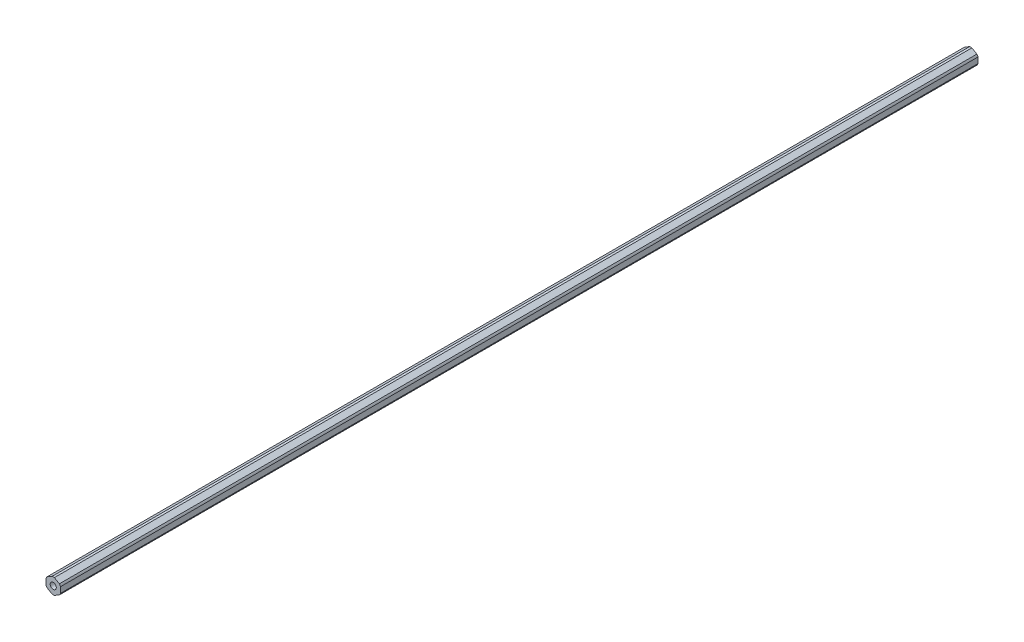
SolidWorks part; units mm, degrees
ref_plane "Front Plane" through (0, 0, 0) normal (0, 0, 1) x (1, 0, 0)
ref_plane "Top Plane" through (0, 0, 0) normal (0, 1, 0) x (1, 0, 0)
ref_plane "Right Plane" through (0, 0, 0) normal (1, 0, 0) x (0, 0, -1)
sketch "Sketch2" plane through (0, 0, 0) normal (0, 0, 1) x (1, 0, 0)
  line L1 (0, 5.4993) -> (-4.7625, 2.7496)
  line L2 (-4.7625, 2.7496) -> (-4.7625, -2.7496)
  line L3 (-4.7625, -2.7496) -> (0, -5.4993)
  line L4 (0, -5.4993) -> (4.7625, -2.7496)
  line L5 (4.7625, -2.7496) -> (4.7625, 2.7496)
  line L6 (4.7625, 2.7496) -> (0, 5.4993)
  circle A0 centre (0, 0) radius 4.7625 construction
  circle A2 centre (0, 0) radius 2.0193
  circle A3 centre (0, 0) radius 5.125
  dimension "D1" = 9.525
  dimension "D2" = 10.25
  dimension "D3" = 4.0386
extrude "Boss-Extrude1" add sketch "Sketch2" along normal mid plane 604.3625 contours L5 A3 L6 L1 L2 L3 L4 A2 region at (0, 4.9851, 0)
equation "\"D2@Sketch2\"=10.25mm"
